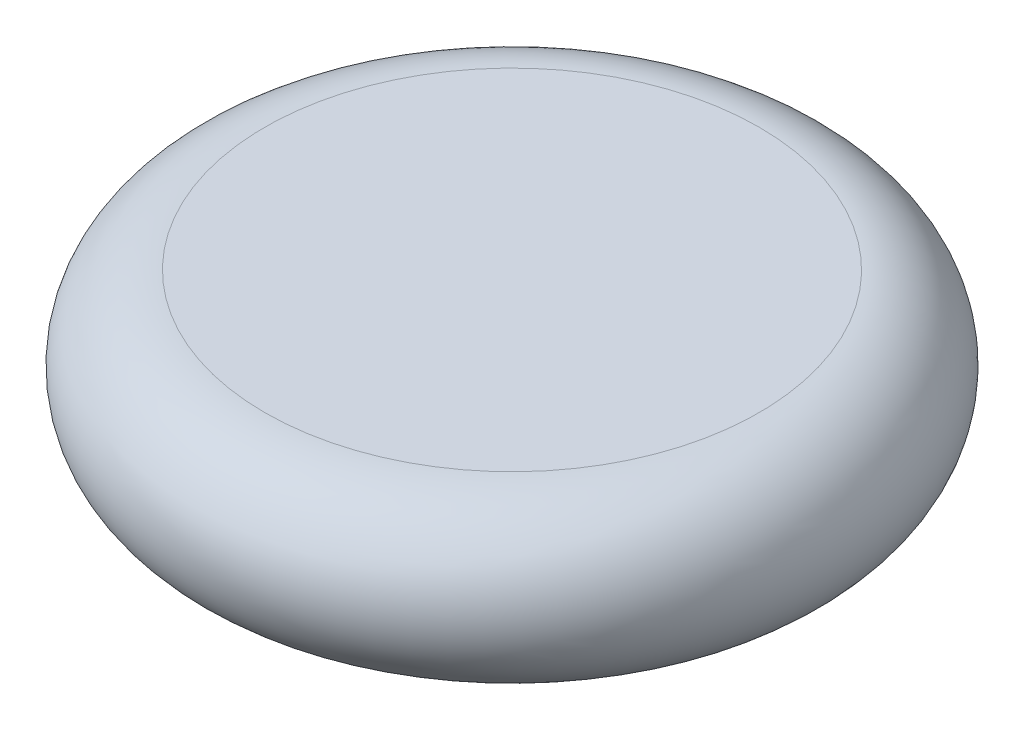
SolidWorks part; units mm, degrees
ref_plane "Front Plane" through (0, 0, 0) normal (0, 0, 1) x (1, 0, 0)
ref_plane "Top Plane" through (0, 0, 0) normal (0, 1, 0) x (1, 0, 0)
ref_plane "Right Plane" through (0, 0, 0) normal (1, 0, 0) x (0, 0, -1)
sketch "Sketch1" plane through (0, 0, 0) normal (0, 0, 1) x (1, 0, 0)
  line L0 (0, 166.6667) -> (0, -500)
  line L1 (0, -500) -> (1000, -500)
  line L3 (0, 166.6667) -> (1000, 166.6667)
  arc A0 (1000, -500) -> (1000, 166.6667) centre (1000, -166.6667) ccw
  point P0 (0, 0)
  dimension "D1" = 1000
  dimension "D2" = 666.6667
  dimension "D3" = 1000
ref_axis "Axis1" through (0, 550, 0) along (0, -1, 0)
revolve "Revolve2" add sketch "Sketch1" angle 360 about axis through (0, 550, 0) along (0, -1, 0)
